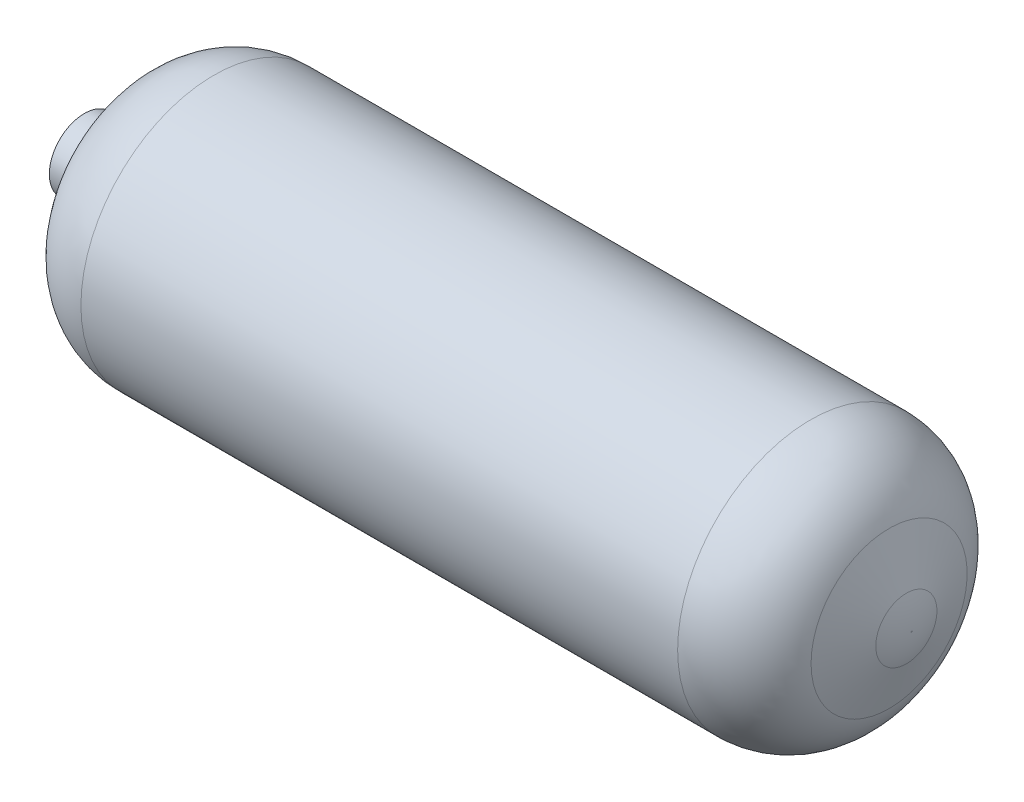
SolidWorks part; units mm, degrees
material "6061-T6 (SS)"
ref_plane "Front Plane" through (0, 0, 0) normal (0, 0, 1) x (1, 0, 0)
ref_plane "Top Plane" through (0, 0, 0) normal (0, 1, 0) x (1, 0, 0)
ref_plane "Right Plane" through (0, 0, 0) normal (1, 0, 0) x (0, 0, -1)
sketch "Sketch1" plane through (0, 0, 0) normal (0, 0, 1) x (1, 0, 0)
  line L0 (-0.2756, 0.129) -> (0.3032, 0.129)
  line L1 (-0.4012, 0.034) -> (-0.4012, 0)
  line L2 (-0.4012, 0.034) -> (-0.3773, 0.034)
  line L4 (-0.3729, 0.0367) -> (-0.3487, 0.0842)
  line L5 (-0.4012, 0) -> (0.4012, 0) construction
  line L6 (0.3794, 0.0757) -> (0.3961, 0.0297)
  line L7 (-0.4012, 0) -> (0.4012, 0)
  line L8 (0.4012, 0) -> (0.4012, 0.0006)
  arc A0 (-0.2756, 0.129) -> (-0.3487, 0.0842) centre (-0.2756, 0.047) ccw
  arc A1 (0.3032, 0.129) -> (0.3794, 0.0757) centre (0.3032, 0.048) cw
  arc A2 (0.4012, 0.0006) -> (0.3961, 0.0297) centre (0.3163, 0.0006) ccw
  arc A3 (-0.3729, 0.0367) -> (-0.3773, 0.034) centre (-0.3773, 0.039) cw
  point P6 (-0.3742, 0.034)
  dimension "D8" = 0.082
  dimension "D11" = 0.081
  dimension "D13" = 0.085
  dimension "D6" = 0.005
  dimension "D2" = 0.2756
  dimension "D3" = 0.034
  dimension "D4" = 0.3032
  dimension "D5" = 0.027
  dimension "D7" = 117
  dimension "D9" = 0.8025
  dimension "D10" = 110
revolve "Revolve2" add sketch "Sketch1" angle 360 about L7 region at (0.0088, 0.062, 0)
scale "Scale1" scale about origin uniform scaling yes scale factor 649.767462
shell "Shell2" thickness 5.588
